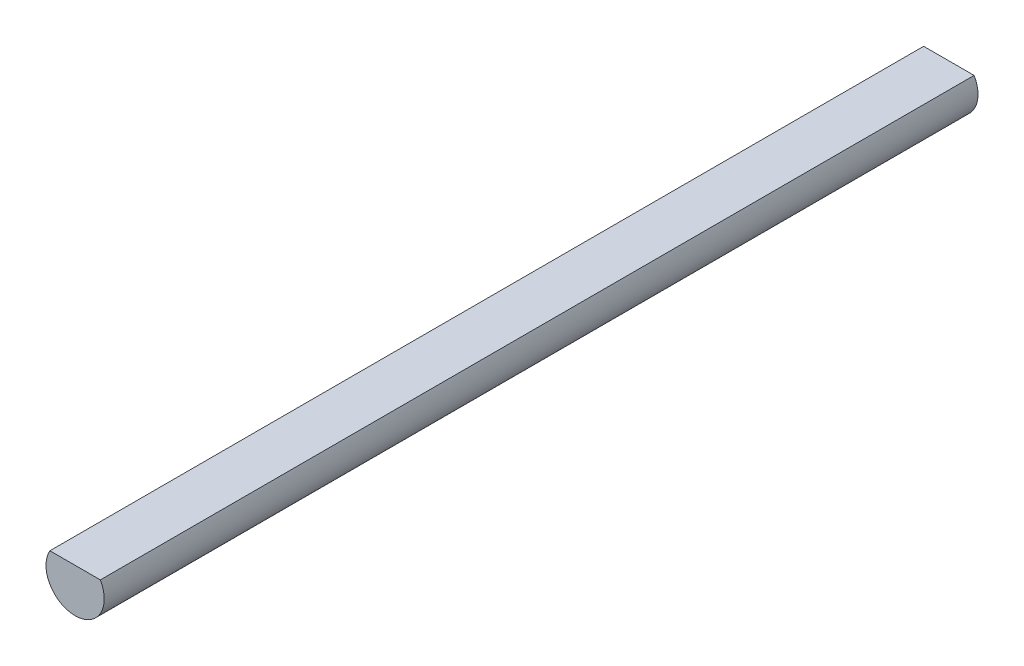
SolidWorks part; units mm, degrees
ref_plane "Front Plane" through (0, 0, 0) normal (0, 0, 1) x (1, 0, 0)
ref_plane "Top Plane" through (0, 0, 0) normal (0, 1, 0) x (1, 0, 0)
ref_plane "Right Plane" through (0, 0, 0) normal (1, 0, 0) x (0, 0, -1)
sketch "Sketch1" plane through (0, 0, 0) normal (0, 0, 1) x (1, 0, 0)
  circle A0 centre (0, 0) radius 2
  dimension "D1" = 4
extrude "Boss-Extrude1" add sketch "Sketch1" along normal blind 60
sketch "Sketch2" plane through (0, 0, 0) normal (0, 0, -1) x (-1, 0, 0)
  point P0 (0, 0)
sketch "Sketch3" plane through (0, 0, 60) normal (0, 0, 1) x (1, 0, 0)
  line L1 (-1.7321, 1) -> (1.7321, 1)
  arc A2 (1.7321, 1) -> (-1.7321, 1) centre (0, 0) ccw
  dimension "D2" = 4
  dimension "D1" = 1
extrude "Cut-Extrude1" cut sketch "Sketch3" against normal through all
